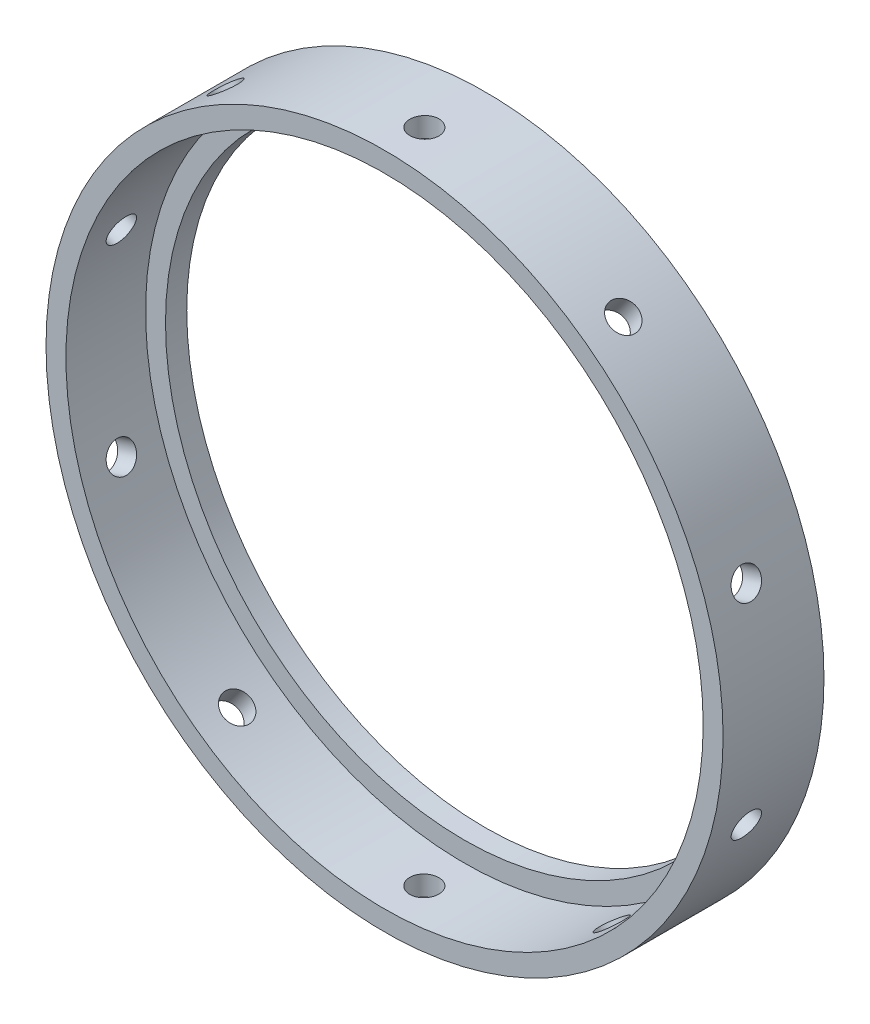
SolidWorks part; units mm, degrees
ref_plane "Front Plane" through (0, 0, 0) normal (0, 0, 1) x (1, 0, 0)
ref_plane "Top Plane" through (0, 0, 0) normal (0, 1, 0) x (1, 0, 0)
ref_plane "Right Plane" through (0, 0, 0) normal (1, 0, 0) x (0, 0, -1)
sketch "Sketch1" plane through (0, 0, 0) normal (0, 0, 1) x (1, 0, 0)
  circle A0 centre (0, 0) radius 76.2
  circle A1 centre (0, 0) radius 80.9625
  dimension "D1" = 152.4
  dimension "D2" = 161.925
extrude "Boss-Extrude1" add sketch "Sketch1" along normal blind 19.05
sketch "Sketch2" plane through (0, 0, 0) normal (0, 1, 0) x (1, 0, 0)
  line L0 (76.2, 0) -> (-76.2, 0) construction
  line L1 (0, -2.0807) -> (0, -15.8358) construction
  circle A0 centre (0, -9.525) radius 3.4782
  dimension "D1" = 9.525
extrude "Cut-Extrude1" cut sketch "Sketch2" against normal through all
ref_axis "Axis1" through (0, 0, 2.0807) along (0, 0, 1)
pattern_circular "CirPattern1" count 10 over 360 about axis through (0, 0, 2.0807) along (0, 0, 1) of "Cut-Extrude1"
sketch "Sketch3" plane through (0, 0, 0) normal (0, 0, -1) x (-1, 0, 0)
  circle A0 centre (0, 0) radius 80.9625
  circle A1 centre (0, 0) radius 71.4375
  dimension "D1" = 161.925
  dimension "D2" = 142.875
extrude "Boss-Extrude2" add sketch "Sketch3" along normal blind 5.08
